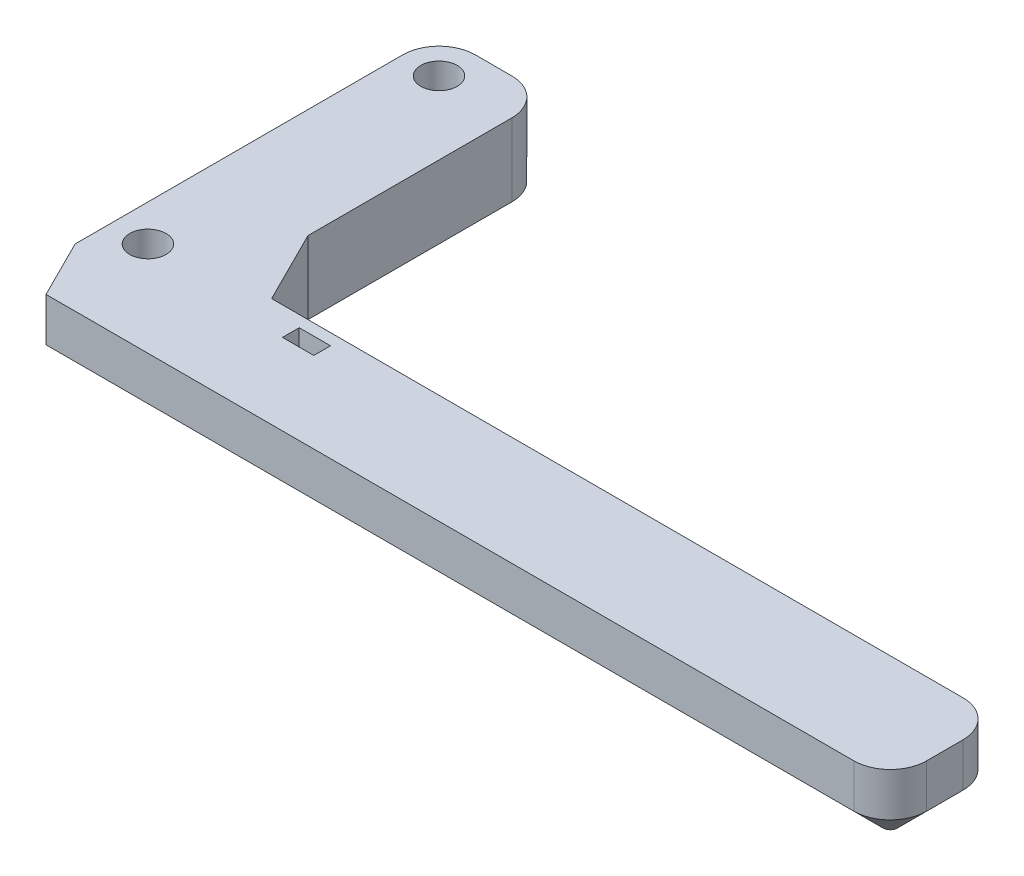
SolidWorks part; units mm, degrees
ref_plane "Front Plane" through (0, 0, 0) normal (0, 0, 1) x (1, 0, 0)
ref_plane "Top Plane" through (0, 0, 0) normal (0, 1, 0) x (1, 0, 0)
ref_plane "Right Plane" through (0, 0, 0) normal (1, 0, 0) x (0, 0, -1)
sketch "Sketch1" plane through (0, 0, 0) normal (0, 1, 0) x (1, 0, 0)
  line L0 (0, -25) -> (0, 25)
  line L1 (0, 25) -> (15, 25)
  line L2 (15, 25) -> (15, -8)
  line L4 (5, 25) -> (5, -25) construction
  line L7 (120, -18) -> (35, -18)
  line L9 (25.51, -19.72) -> (25.51, -21.72) construction
  line L10 (25.51, -21.72) -> (29.51, -21.72) construction
  line L11 (29.51, -21.72) -> (29.51, -19.72) construction
  line L12 (29.51, -19.72) -> (25.51, -19.72) construction
  line L15 (20, -18) -> (32, -18)
  line L16 (32, -18) -> (35, -18)
  line L17 (15, -8) -> (20, -18)
  line L22 (29.66, -19.57) -> (25.36, -19.57)
  line L23 (25.36, -19.57) -> (25.36, -21.87)
  line L24 (25.36, -21.87) -> (29.66, -21.87)
  line L25 (29.66, -21.87) -> (29.66, -19.57)
  line L26 (25.36, -21.87) -> (25.51, -21.72) construction
  line L27 (25.36, -19.57) -> (25.51, -19.72) construction
  line L28 (29.51, -19.72) -> (29.66, -19.57) construction
  line L29 (29.51, -21.72) -> (29.66, -21.87) construction
  line L30 (0, -25) -> (4, -33)
  line L31 (4, -33) -> (120, -33)
  line L32 (120, -33) -> (120, -18)
  circle A0 centre (5, 20) radius 2.5
  circle A1 centre (5, -20) radius 2.5
  point P3 (0, 0)
  dimension "D3" = 5
  dimension "D1" = 50
  dimension "D2" = 15
  dimension "D4" = 40
  dimension "D5" = 20
  dimension "D6" = 33
  dimension "D7" = 15
  dimension "D8" = 5
  dimension "D9" = 8
  dimension "D10" = 5
  dimension "D11" = 4
  dimension "D12" = 2
  dimension "D13" = 25.51
  dimension "D14" = 3
  dimension "D15" = 1.72
  dimension "D17" = 10
  dimension "D18" = 0.2121
  dimension "D19" = 0.2121
  dimension "D20" = 0.2121
  dimension "D21" = 0.2121
  dimension "D22" = 1.72
  dimension "D16" = 0.15
extrude "Boss-Extrude1" add sketch "Sketch1" along normal blind 10
sketch "Sketch2" plane through (0, 0, 0) normal (0, -1, 0) x (1, 0, 0)
  line L0 (10, 34.3957) -> (10, -25)
  line L2 (15, -25) -> (0, -25) construction
  line L3 (10, -25) -> (14, -25)
  line L4 (14, -25) -> (14, 34.3957)
  line L5 (14, 34.3957) -> (10, 34.3957)
  line L6 (0, -25) -> (0, 25) construction
  dimension "D1" = 10
  dimension "D2" = 4
extrude "Cut-Extrude1" cut sketch "Sketch2" against normal blind 3
fillet "Fillet3" radius 5 4 edges at (120, 5, 33) (120, 5, 18) (0, 5, -25) (15, 5, -25)
chamfer "Chamfer2" distance 4 angle 45 5 edges at (120, 0, 25.5) (64.5, 0, 33) (118.5355, 0, 31.5355) (118.5355, 0, 19.4645) (67.5, 0, 18)
